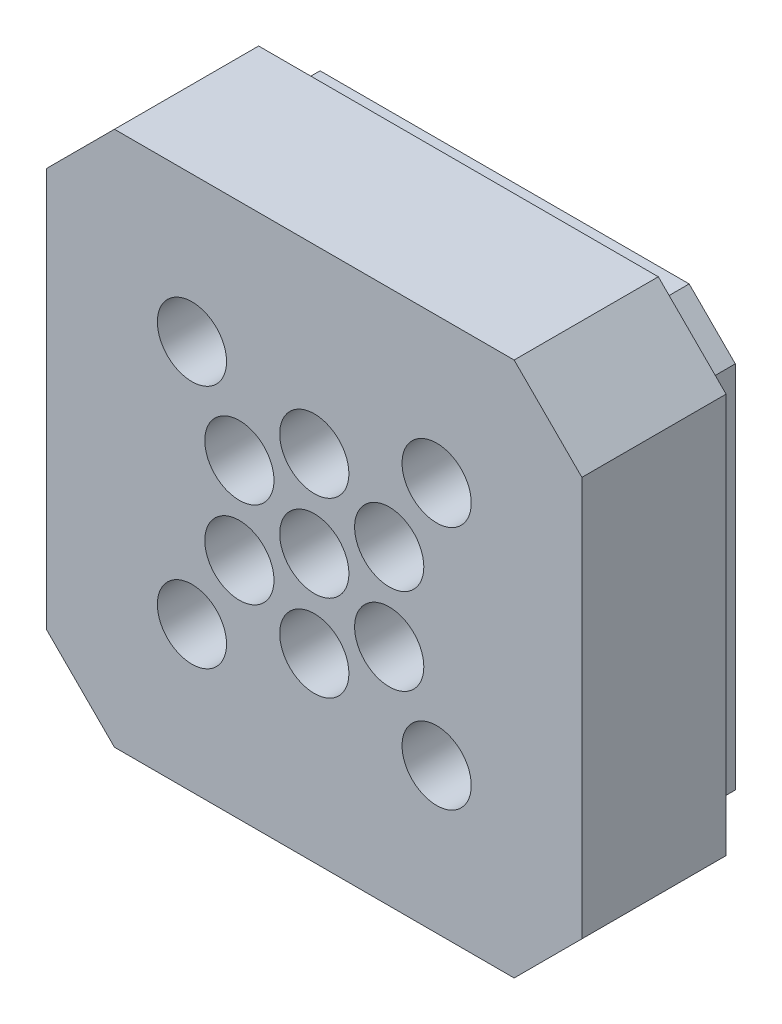
SolidWorks part; units mm, degrees
material "6061-T6 (SS)"
ref_plane "Front Plane" through (0, 0, 0) normal (0, 0, 1) x (1, 0, 0)
ref_plane "Top Plane" through (0, 0, 0) normal (0, 1, 0) x (1, 0, 0)
ref_plane "Right Plane" through (0, 0, 0) normal (1, 0, 0) x (0, 0, -1)
sketch "Sketch1" plane through (0, 0, 0) normal (0, 0, 1) x (1, 0, 0)
  line L1 (0, 0) -> (40, 0)
  line L2 (0, 0) -> (0, 40)
  line L3 (0, 40) -> (40, 40)
  line L4 (40, 0) -> (40, 40)
  dimension "D2" = 40
extrude "Boss-Extrude1" add sketch "Sketch1" along normal blind 10
sketch "Sketch18" plane through (0, 0, 10) normal (0, 0, 1) x (1, 0, 0)
  line L0 (40, 0) -> (40, 40) construction
  line L1 (0, 40) -> (0, 0) construction
  line L2 (0, 0) -> (40, 0) construction
  circle A0 centre (20, 20) radius 20
  point P1 (20, 20)
hole_wizard "Ø6.0mm Dowel Hole1" positions "Sketch18" profile "Sketch17" hole size "Ø6.0" standard "DIN" end condition through all
sketch "Sketch17" plane through (20, 20, 10) normal (1, 0, 0) x (0, -1, 0)
  line L0 (0, 0) -> (0, 10)
  line L1 (0, 10) -> (3, 10)
  line L2 (3, 10) -> (3, 0)
  line L5 (3, 0) -> (0, 0)
  line L11 (0, -6.35) -> (0, 107.95) construction
  dimension "Thru Hole Dia." = 6
  dimension "Thru Hole Depth" = 10
sketch "Sketch10" plane through (0, 0, 10) normal (0, 0, 1) x (1, 0, 0)
  point P5 (20, 27.5)
  point P12 (26.4952, 23.75)
  point P13 (26.4952, 16.25)
  point P14 (20, 12.5)
  point P15 (13.5048, 16.25)
  point P16 (13.5048, 23.75)
  dimension "D2" = 6
hole_wizard "CSK for M3 Hex Socket Countersunk Head Screw1" positions "Sketch10" profile "Sketch11" countersink size "M3" standard "DIN" end condition through all
sketch "Sketch11" plane through (20, 27.5, 10) normal (1, 0, 0) x (0, -1, 0)
  line L0 (0, 0) -> (0, 10)
  line L1 (0, 10) -> (1.7, 10)
  line L2 (1.7, 10) -> (1.7, 1.77)
  line L3 (1.7, 1.77) -> (3.47, 0)
  line L5 (3.47, 0) -> (0, 0)
  line L6 (-1.7, 1.77) -> (-3.47, 0) construction
  line L11 (0, -6.35) -> (0, 107.95) construction
  dimension "Thru Hole Dia." = 3.4
  dimension "Thru Hole Depth" = 10
  dimension "Near C'Sink Dia." = 6.94
  dimension "Near C'Sink Angle" = 90
sketch "Sketch12" plane through (0, 0, 10) normal (0, 0, 1) x (1, 0, 0)
  point P4 (9.3934, 30.6066)
  point P11 (30.6066, 30.6066)
  point P12 (30.6066, 9.3934)
  point P13 (9.3934, 9.3934)
  dimension "D2" = 4
hole_wizard "Tap Drill for M4 Tap1" positions "Sketch12" profile "Sketch13" hole size "M4" standard "DIN" end condition through all
sketch "Sketch13" plane through (9.3934, 30.6066, 10) normal (1, 0, 0) x (0, -1, 0)
  line L0 (0, 0) -> (0, 10)
  line L1 (0, 10) -> (1.65, 10)
  line L2 (1.65, 10) -> (1.65, 0)
  line L5 (1.65, 0) -> (0, 0)
  line L11 (0, -6.35) -> (0, 107.95) construction
  dimension "Thru Hole Dia." = 3.3
  dimension "Thru Hole Depth" = 10
chamfer "Chamfer1" distance 4 angle 45 4 edges at (40, 0, 5) (40, 40, 5) (0, 0, 5) (0, 40, 5)
chamfer "Chamfer2" distance 0.6 angle 45 8 edges at (40, 20, 10) (38, 38, 10) (38, 2, 10) (20, 0, 10) (2, 2, 10) (0, 20, 10) (2, 38, 10) (20, 40, 10)
sketch "Sketch19" plane through (0, 0, 10) normal (0, 0, 1) x (1, 0, 0)
  line L0 (40.2, 3.9172) -> (40.2, 36.0828)
  line L1 (40.2, 36.0828) -> (36.0828, 40.2)
  line L2 (36.0828, 40.2) -> (3.9172, 40.2)
  line L3 (3.9172, 40.2) -> (-0.2, 36.0828)
  line L4 (-0.2, 36.0828) -> (-0.2, 3.9172)
  line L5 (-0.2, 3.9172) -> (3.9172, -0.2)
  line L6 (3.9172, -0.2) -> (36.0828, -0.2)
  line L7 (36.0828, -0.2) -> (40.2, 3.9172)
  line L8 (40, 4) -> (40, 36)
  line L9 (36, 0) -> (40, 4)
  line L10 (4, 0) -> (36, 0)
  line L11 (0, 4) -> (4, 0)
  line L12 (0, 36) -> (0, 4)
  line L13 (4, 40) -> (0, 36)
  line L14 (36, 40) -> (4, 40)
  line L15 (40, 36) -> (36, 40)
  line L16 (40, 4) -> (40, 36) construction
  line L17 (36, 0) -> (40, 4) construction
  line L18 (4, 0) -> (36, 0) construction
  line L19 (0, 4) -> (4, 0) construction
  line L20 (0, 36) -> (0, 4) construction
  line L21 (4, 40) -> (0, 36) construction
  line L22 (36, 40) -> (4, 40) construction
  line L23 (40, 36) -> (36, 40) construction
  line L24 (43.2, 2.6745) -> (43.2, 37.3255)
  line L25 (43.2, 37.3255) -> (37.3255, 43.2)
  line L26 (37.3255, 43.2) -> (2.6745, 43.2)
  line L27 (2.6745, 43.2) -> (-3.2, 37.3255)
  line L28 (-3.2, 37.3255) -> (-3.2, 2.6745)
  line L29 (-3.2, 2.6745) -> (2.6745, -3.2)
  line L30 (2.6745, -3.2) -> (37.3255, -3.2)
  line L31 (37.3255, -3.2) -> (43.2, 2.6745)
  dimension "D3" = 3
  dimension "D1" = 0
  dimension "D2" = 0.2
extrude "Boss-Extrude2" add sketch "Sketch19" against normal blind 6 separate body
sketch "Sketch20" plane through (0, 0, 10) normal (0, 0, 1) x (1, 0, 0)
  line L8 (37.3255, -3.2) -> (43.2, 2.6745)
  line L9 (43.2, 2.6745) -> (43.2, 37.3255)
  line L10 (43.2, 37.3255) -> (37.3255, 43.2)
  line L11 (37.3255, 43.2) -> (2.6745, 43.2)
  line L12 (2.6745, 43.2) -> (-3.2, 37.3255)
  line L13 (-3.2, 37.3255) -> (-3.2, 2.6745)
  line L14 (-3.2, 2.6745) -> (2.6745, -3.2)
  line L15 (2.6745, -3.2) -> (37.3255, -3.2)
  line L16 (37.3255, -3.2) -> (43.2, 2.6745)
  line L17 (43.2, 2.6745) -> (43.2, 37.3255)
  line L18 (43.2, 37.3255) -> (37.3255, 43.2)
  line L19 (37.3255, 43.2) -> (2.6745, 43.2)
  line L20 (2.6745, 43.2) -> (-3.2, 37.3255)
  line L21 (-3.2, 37.3255) -> (-3.2, 2.6745)
  line L22 (-3.2, 2.6745) -> (2.6745, -3.2)
  line L23 (2.6745, -3.2) -> (37.3255, -3.2)
  dimension "D1" = 0
extrude "Boss-Extrude3" add sketch "Sketch20" along normal blind 6.5
sketch "Sketch23" plane through (0, 0, 16.5) normal (0, 0, 1) x (1, 0, 0)
  point P0 (30.6066, 30.6066)
  point P3 (9.3934, 30.6066)
  point P6 (20, 27.5)
  point P9 (26.4952, 23.75)
  point P12 (26.4952, 16.25)
  point P15 (30.6066, 9.3934)
  point P18 (9.3934, 9.3934)
  point P21 (13.5048, 23.75)
  point P24 (13.5048, 16.25)
  point P27 (20, 12.5)
  point P30 (20, 20)
hole_wizard "Ø6.0mm Dowel Hole2" positions "Sketch23" profile "Sketch22" hole size "Ø6.0" standard "DIN"
sketch "Sketch22" plane through (30.6066, 30.6066, 16.5) normal (1, 0, 0) x (0, -1, 0)
  line L0 (0, 0) -> (0, 8.3026)
  line L1 (0, 8.3026) -> (3, 6.5)
  line L2 (3, 6.5) -> (3, 0)
  line L5 (3, 0) -> (0, 0)
  line L10 (0, 8.3026) -> (-3, 6.5) construction
  line L11 (0, -6.35) -> (0, 107.95) construction
  dimension "Hole Dia." = 6
  dimension "Hole Depth" = 6.5
  dimension "Drill Angle" = 118
